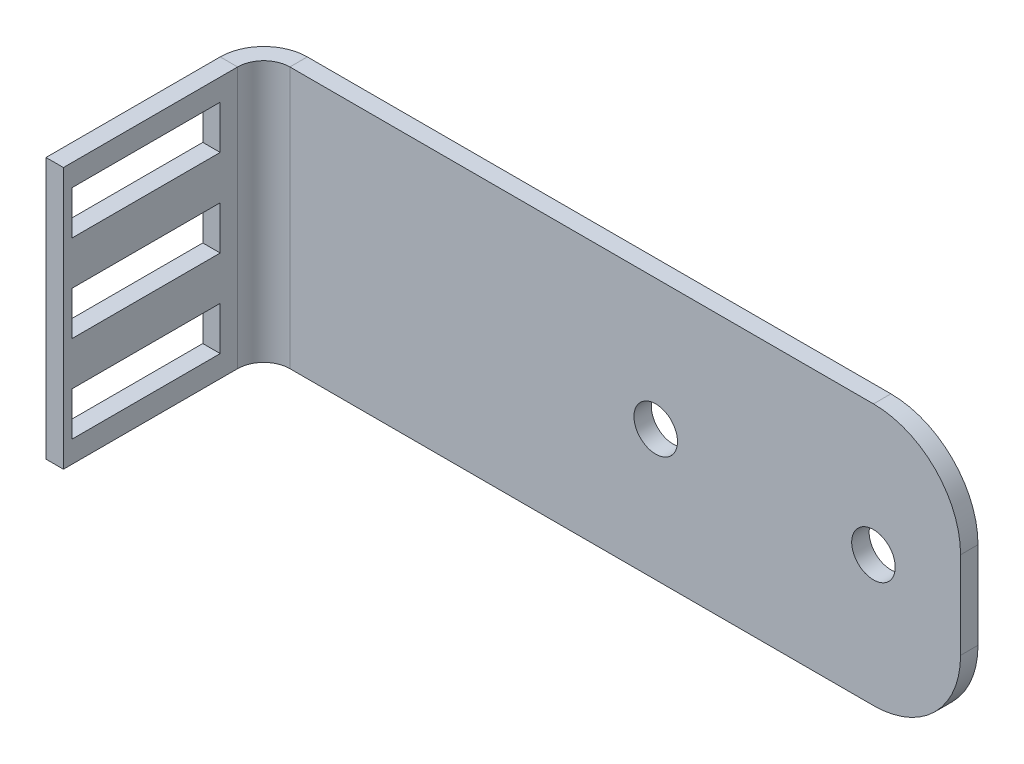
SolidWorks part; units mm, degrees
note: The reader was unsure of these and kept them because the rebuilt part matched: flange length of "Edge-Flange1".
ref_plane "Front Plane" through (0, 0, 0) normal (0, 0, 1) x (1, 0, 0)
ref_plane "Top Plane" through (0, 0, 0) normal (0, 1, 0) x (1, 0, 0)
ref_plane "Right Plane" through (0, 0, 0) normal (1, 0, 0) x (0, 0, -1)
sketch "Sketch1" plane through (0, 0, 0) normal (0, 0, 1) x (1, 0, 0)
  line L1 (-40, 15) -> (40, 15)
  line L2 (-40, 15) -> (-40, -15)
  line L3 (-40, -15) -> (40, -15)
  line L4 (40, 15) -> (40, -15)
  line L5 (-40, 15) -> (40, -15) construction
  line L6 (-40, -15) -> (40, 15) construction
  circle A3 centre (30, 0) radius 2.5
  circle A4 centre (5, 0) radius 2.5
  point P0 (0, 0)
  dimension "D5" = 5
  dimension "D7" = 5
  dimension "D1" = 30
  dimension "D2" = 80
  dimension "D8" = 25
  dimension "D9" = 10
base flange "Base-Flange1" sketch "Sketch1" thickness 2 reverse thickness direction no parameters "D1"=0.7366
fillet "Fillet1" radius 10 2 edges at (40, -15, -1) (40, 15, -1)
edge flange "Edge-Flange1" sketch "Sketch8" flange angle 90 flange length 23 flange position material outside bend radius 3 thickness 2 relief rectangular parameters "D6"=10
sketch "Sketch8" plane through (-40, 0, 0) normal (-1, 0, 0) x (0, -1, 0)
  line L0 (-15, 0) -> (15, 0) construction
  line L1 (-15, 0) -> (15, 0)
  line L2 (-15, 0) -> (-15, 23)
  line L3 (-15, 23) -> (15, 23)
  line L4 (15, 23) -> (15, 0)
bend "EdgeBend1" bend radius 3 bend angle 90 parameters "D5"=1
sketch "Sketch9" plane through (-42, 0, 0) normal (-1, 0, 0) x (0, 0, 1)
  line L0 (3, -15) -> (3, 15) construction
  line L1 (5, 7.5) -> (22, 7.5)
  line L2 (5, 7.5) -> (5, 12.5)
  line L3 (5, 12.5) -> (22, 12.5)
  line L4 (22, 7.5) -> (22, 12.5)
  line L5 (5, 7.5) -> (22, 12.5) construction
  line L6 (5, 12.5) -> (22, 7.5) construction
  line L7 (23, 15) -> (3, 15) construction
  line L8 (5, -2.5) -> (5, 2.5)
  line L9 (5, -2.5) -> (22, -2.5)
  line L10 (22, -2.5) -> (22, 2.5)
  line L11 (5, 2.5) -> (22, 2.5)
  line L12 (5, -12.5) -> (5, -7.5)
  line L13 (5, -12.5) -> (22, -12.5)
  line L14 (22, -12.5) -> (22, -7.5)
  line L15 (5, -7.5) -> (22, -7.5)
  point P0 (13.5, 10)
  dimension "D1" = 5
  dimension "D2" = 17
  dimension "D3" = 10.5
  dimension "D4" = 5
  dimension "D6" = 5
  dimension "D5" = 3
extrude "Cut-Extrude1" cut sketch "Sketch9" against normal blind 10 normal cut yes
sketch "Bend-Lines1" [suppressed] plane through (0, 0, 0) normal (0, 1, 0) x (1, 0, 0)
sketch "Bounding-Box1" [suppressed] plane through (0, 0, 0) normal (0, 1, 0) x (1, 0, 0)
sheet metal parameters "Sheet-Metal1" thickness 2 parameters "D1"=0.7366
flat pattern "Flat-Pattern1" [suppressed]
sketch "Bend-Lines2" plane through (0, 0, 0) normal (0, 1, 0) x (1, 0, 0)
sketch3d "Bounding-Box2" [suppressed]
  line L0 (-40, -15, 0) -> (40, -15, 0) construction
  line L1 (-40, 15, 0) -> (40, 15, 0) construction
  line L2 (-40, -15, 0) -> (-40, 15, 0) construction
  line L3 (40, -15, 0) -> (40, 15, 0) construction
sheet metal parameters "Sheet-Metal2" thickness 2 parameters "D1"=0.7366
flat pattern "Flat-Pattern1"
sketch "Bend-Lines2" plane through (0, 0, 0) normal (0, 0, 1) x (1, 0, 0)
  line L0 (-40.6273, 15) -> (-40.6273, -15) construction
  line L1 (-40.6273, 15) -> (-40.6273, -15) construction
sketch3d "Bounding-Box2" [suppressed]
  line L0 (-51.2546, -15, 0) -> (40, -15, 0) construction
  line L1 (-51.2546, 15, 0) -> (40, 15, 0) construction
  line L2 (-51.2546, -15, 0) -> (-51.2546, 15, 0) construction
  line L3 (40, -15, 0) -> (40, 15, 0) construction
bend of the flat pattern "Flatten-<EdgeBend1>1"
sheet metal parameters "Sheet-Metal3" thickness 2 parameters "D1"=0.7366
flat pattern "Flat-Pattern1"
sketch "Bend-Lines2" plane through (0, 0, 0) normal (0, 0, 1) x (1, 0, 0)
  line L0 (-40.1416, 15) -> (-40.1416, -15) construction
  line L1 (-40.1416, 15) -> (-40.1416, -15) construction
sketch3d "Bounding-Box2" [suppressed]
  line L0 (-63.2832, -15, 0) -> (40, -15, 0) construction
  line L1 (-63.2832, 15, 0) -> (40, 15, 0) construction
  line L2 (-63.2832, -15, 0) -> (-63.2832, 15, 0) construction
  line L3 (40, -15, 0) -> (40, 15, 0) construction
bend of the flat pattern "Flatten-<EdgeBend1>1"
